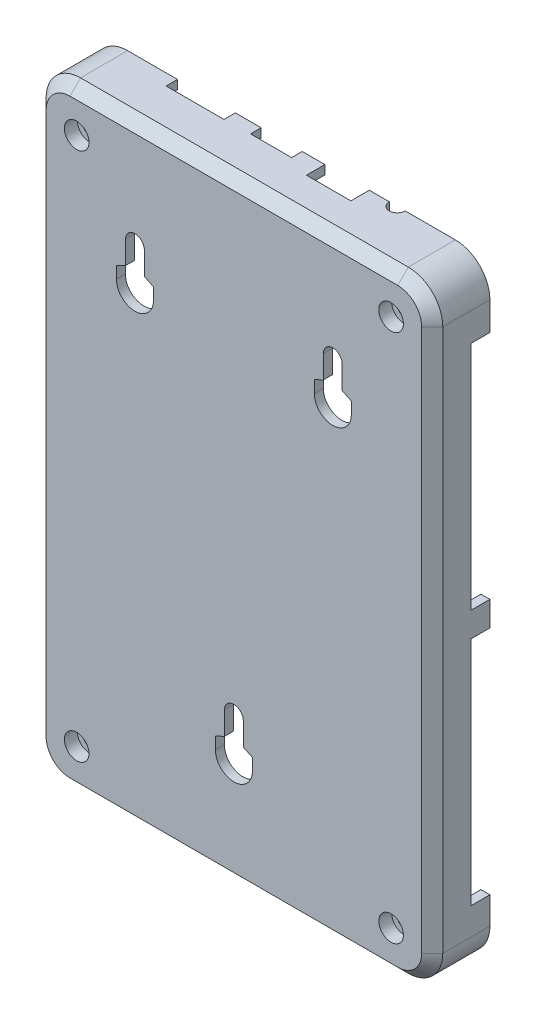
SolidWorks part; units mm, degrees
ref_plane "前基準面" through (0, 0, 0) normal (0, 0, 1) x (1, 0, 0)
ref_plane "上基準面" through (0, 0, 0) normal (0, 1, 0) x (1, 0, 0)
ref_plane "右基準面" through (0, 0, 0) normal (1, 0, 0) x (0, 0, -1)
sketch "草圖1" plane through (0, 0, 0) normal (0, 0, 1) x (1, 0, 0)
  line L0 (-44.3, 60.6) -> (-44.3, -60.6)
  line L1 (-36.6, 60.6) -> (36.6, 60.6) construction
  line L2 (-36.6, 60.6) -> (-36.6, -60.6) construction
  line L3 (-36.6, -60.6) -> (36.6, -60.6) construction
  line L4 (36.6, 60.6) -> (36.6, -60.6) construction
  line L5 (-36.6, 60.6) -> (36.6, -60.6) construction
  line L6 (-36.6, -60.6) -> (36.6, 60.6) construction
  line L7 (-36.6, -68.3) -> (36.6, -68.3)
  line L8 (44.3, -60.6) -> (44.3, 60.6)
  line L9 (36.6, 68.3) -> (-36.6, 68.3)
  arc A0 (-44.3, 60.6) -> (-36.6, 68.3) centre (-36.6, 60.6) cw
  arc A1 (36.6, 68.3) -> (44.3, 60.6) centre (36.6, 60.6) cw
  arc A2 (44.3, -60.6) -> (36.6, -68.3) centre (36.6, -60.6) cw
  arc A3 (-36.6, -68.3) -> (-44.3, -60.6) centre (-36.6, -60.6) cw
  point P0 (0, 0)
  dimension "D3" = 7.7
  dimension "D1" = 121.2
  dimension "D2" = 73.2
  dimension "D4" = 7.7
  dimension "D5" = 7.7
  dimension "D6" = 7.7
  dimension "D7" = 7.7
extrude "填料-伸長1" add sketch "草圖1" along normal blind 12.88
chamfer "導角1" distance 2.36 angle 45 8 edges at (-44.3, 0, 12.88) (0, 68.3, 12.88) (42.0447, 66.0447, 12.88) (44.3, 0, 12.88) (42.0447, -66.0447, 12.88) (0, -68.3, 12.88) (-42.0447, -66.0447, 12.88) (-42.0447, 66.0447, 12.88)
sketch "草圖7" plane through (0, -68.3, 0) normal (0, -1, 0) x (-1, 0, 0)
  line L0 (24.93, 0) -> (14.87, 0) construction
  line L1 (36.6, 0) -> (-36.6, 0) construction
  line L2 (24.93, -5.15) -> (14.87, -5.15)
  line L3 (24.93, 5.15) -> (14.87, 5.15)
  line L7 (36.6, -10.52) -> (36.6, 0) construction
  arc A0 (24.93, -5.15) -> (24.93, 5.15) centre (24.93, 0) ccw
  arc A1 (14.87, 5.15) -> (14.87, -5.15) centre (14.87, 0) ccw
  point P4 (19.9, 0)
  point P9 (30.08, 0)
  dimension "D2" = 5.15
  dimension "D3" = 6.52
  dimension "D1" = 10.06
extrude "除料-伸長4" cut sketch "草圖7" against normal blind 1.13
shell "薄殼1" thickness 2 removed face at (-6.6333, -22.5783, 0)
sketch "草圖2" plane through (0, 0, 12.88) normal (0, 0, 1) x (1, 0, 0)
  line L0 (-26.23, 35.7246) -> (-26.23, 38.3946)
  line L1 (-26.23, 38.3946) -> (-24.2024, 39.37)
  line L2 (44.3, 60.6) -> (44.3, -60.6) construction
  line L3 (-17.97, 35.7246) -> (-17.97, 38.3946)
  line L4 (-17.97, 38.3946) -> (-19.9976, 39.37)
  line L5 (-24.2024, 39.37) -> (-24.2024, 44.5)
  line L6 (-19.9976, 39.37) -> (-19.9976, 44.5)
  line L7 (-24.2024, 44.5) -> (-19.9976, 44.5) construction
  line L8 (36.6, -68.3) -> (-36.6, -68.3) construction
  line L9 (17.97, 35.7246) -> (17.97, 38.3946)
  line L10 (17.97, 38.3946) -> (19.9976, 39.37)
  line L11 (19.9976, 39.37) -> (19.9976, 44.5)
  line L12 (26.23, 35.7246) -> (26.23, 38.3946)
  line L13 (26.23, 38.3946) -> (24.2024, 39.37)
  line L14 (24.2024, 39.37) -> (24.2024, 44.5)
  line L15 (4.13, -44.2754) -> (4.13, -41.6054)
  line L16 (4.13, -41.6054) -> (2.1024, -40.63)
  line L17 (2.1024, -40.63) -> (2.1024, -35.5)
  line L18 (-4.13, -44.2754) -> (-4.13, -41.6054)
  line L19 (-4.13, -41.6054) -> (-2.1024, -40.63)
  line L20 (-2.1024, -40.63) -> (-2.1024, -35.5)
  line L21 (-2.1024, -35.5) -> (2.1024, -35.5) construction
  line L22 (19.9976, 44.5) -> (24.2024, 44.5) construction
  arc A3 (-26.23, 35.7246) -> (-17.97, 35.7246) centre (-22.1, 35.7246) ccw
  arc A4 (26.23, 35.7246) -> (17.97, 35.7246) centre (22.1, 35.7246) cw
  arc A5 (4.13, -44.2754) -> (-4.13, -44.2754) centre (0, -44.2754) cw
  arc A6 (-24.2024, 44.5) -> (-19.9976, 44.5) centre (-22.1, 44.5) cw
  arc A7 (19.9976, 44.5) -> (24.2024, 44.5) centre (22.1, 44.5) cw
  arc A8 (-2.1024, -35.5) -> (2.1024, -35.5) centre (0, -35.5) cw
  dimension "D1" = 4.13
  dimension "D10" = 80
  dimension "D15" = 32.8
  dimension "D2" = 2.67
  dimension "D3" = 2.25
  dimension "D4" = 22.2
  dimension "D5" = 44.2
  dimension "D6" = 44.3
  dimension "D7" = 115.69
  dimension "D8" = 115.69
  dimension "D9" = 5.13
  dimension "D11" = 115.69
  dimension "D12" = 115.69
  dimension "D13" = 115.69
  dimension "D14" = 115.69
extrude "除料-伸長1" cut sketch "草圖2" against normal blind 4.34 contours A6 L5 L1 L0 A3 L3 L4 L6 | A7 L11 L10 L9 A4 L12 L13 L14 | A8 L20 L19 L18 A5 L15 L16 L17 region at (-22.1, 38.1508, 12.88) region at (22.1, 38.1508, 12.88) region at (0, -41.8492, 12.88)
sketch "草圖8" plane through (0, -67.17, 0) normal (0, -1, 0) x (-1, 0, 0)
  line L0 (9.72, 0) -> (30.08, 0) construction
  circle A0 centre (14.87, 0) radius 1.93
  dimension "D1" = 3.86
extrude "除料-伸長5" cut sketch "草圖8" against normal up to next
pattern_linear "直線複製排列1" count 2 spacing 10.06 along (-1, 0, 0) of "除料-伸長5"
sketch "草圖9" plane through (44.3, 0, 0) normal (1, 0, 0) x (0, 0, -1)
  line L0 (0, -60.6) -> (0, 60.6) construction
  line L1 (0, -54.52) -> (-4.17, -54.52)
  line L2 (0, -54.52) -> (0, -2.91)
  line L3 (0, -2.91) -> (-4.17, -2.91)
  line L4 (-4.17, -54.52) -> (-4.17, -2.91)
  line L5 (-10.52, -68.3) -> (0, -68.3) construction
  dimension "D1" = 4.17
  dimension "D2" = 13.78
  dimension "D3" = 51.61
extrude "除料-伸長6" cut sketch "草圖9" against normal up to next
pattern_linear "直線複製排列2" count 2 spacing 57.15 along (0, 1, 0) of "除料-伸長6"
sketch "草圖11" plane through (0, 68.3, 0) normal (0, 1, 0) x (1, 0, 0)
  line L0 (36.6, 0) -> (-36.6, 0) construction
  line L1 (44.3, -10.52) -> (44.3, 0) construction
  circle A0 centre (23.61, 0) radius 1.78
  dimension "D1" = 3.56
  dimension "D2" = 20.69
extrude "除料-伸長7" cut sketch "草圖11" against normal up to next
sketch "草圖12" plane through (0, 68.3, 0) normal (0, 1, 0) x (1, 0, 0)
  line L0 (21.83, 0) -> (-36.6, 0) construction
  line L1 (17.37, 0) -> (7.45, 0)
  line L2 (17.37, 0) -> (17.37, -4.12)
  line L3 (17.37, -4.12) -> (7.45, -4.12)
  line L4 (7.45, 0) -> (7.45, -4.12)
  arc A0 (21.83, 0) -> (25.39, 0) centre (23.61, 0) ccw construction
  dimension "D3" = 6.24
  dimension "D1" = 4.12
  dimension "D2" = 9.92
extrude "除料-伸長8" cut sketch "草圖12" against normal up to next
sketch "草圖13" plane through (0, 68.3, 0) normal (0, 1, 0) x (1, 0, 0)
  line L0 (7.45, 0) -> (-36.6, 0) construction
  line L1 (2.38, 0) -> (-6.79, 0)
  line L2 (2.38, 0) -> (2.38, -2.37)
  line L3 (2.38, -2.37) -> (-6.79, -2.37)
  line L4 (-6.79, 0) -> (-6.79, -2.37)
  dimension "D1" = 5.07
  dimension "D2" = 9.17
  dimension "D3" = 2.37
extrude "除料-伸長9" cut sketch "草圖13" against normal up to next
sketch "草圖14" plane through (0, 68.3, 0) normal (0, 1, 0) x (1, 0, 0)
  line L0 (-6.79, 0) -> (-36.6, 0) construction
  line L1 (-12.55, 0) -> (-25.48, 0)
  line L2 (-12.55, 0) -> (-12.55, -2.54)
  line L3 (-12.55, -2.54) -> (-25.48, -2.54)
  line L4 (-25.48, 0) -> (-25.48, -2.54)
  line L5 (-6.79, 0) -> (-6.79, -2.37) construction
  dimension "D1" = 12.93
  dimension "D2" = 2.54
  dimension "D3" = 5.76
extrude "除料-伸長10" cut sketch "草圖14" against normal up to next
sketch "草圖15" plane through (0, 0, 0) normal (0, 0, -1) x (-1, 0, 0)
  line L0 (44.3, 60.6) -> (44.3, -60.6) construction
  line L1 (44.3, 53.4) -> (42.3, 53.4)
  line L2 (44.3, 53.4) -> (44.3, -52.98)
  line L3 (44.3, -52.98) -> (42.3, -52.98)
  line L4 (42.3, 53.4) -> (42.3, -52.98)
  line L6 (42.3, 60.6) -> (42.3, -60.6) construction
  arc A0 (36.6, -68.3) -> (44.3, -60.6) centre (36.6, -60.6) ccw construction
  dimension "D1" = 7.62
  dimension "D2" = 14.9
extrude "填料-伸長2" add sketch "草圖15" along normal blind 3.16
sketch "草圖16" plane through (-44.3, 0, 0) normal (-1, 0, 0) x (0, 0, 1)
  line L1 (-3.16, 53.4) -> (4.5, 53.4)
  line L2 (-3.16, 53.4) -> (-3.16, -25.03)
  line L3 (-3.16, -25.03) -> (4.5, -25.03)
  line L4 (4.5, 53.4) -> (4.5, -25.03)
  line L5 (-3.16, -52.98) -> (-3.16, 53.4) construction
  line L6 (10.52, 68.3) -> (0, 68.3) construction
  dimension "D1" = 7.66
  dimension "D2" = 14.9
  dimension "D3" = 78.43
extrude "除料-伸長11" cut sketch "草圖16" against normal up to next
sketch "草圖17" plane through (-44.3, 0, 0) normal (-1, 0, 0) x (0, 0, 1)
  line L0 (-3.16, -52.98) -> (-3.16, -25.03) construction
  line L1 (-3.16, -52.98) -> (0, -52.98) construction
  circle A0 centre (-3.16, -33.05) radius 3.53
  circle A1 centre (-3.16, -44.48) radius 3.53
  dimension "D1" = 7.06
  dimension "D2" = 7.06
  dimension "D3" = 8.5
  dimension "D4" = 11.43
extrude "除料-伸長12" cut sketch "草圖17" against normal up to next
sketch "草圖18" plane through (0, 0, 10.88) normal (0, 0, -1) x (-1, 0, 0)
  line L0 (36.6, -65.1116) -> (-36.6, -65.1116) construction
  line L1 (41.1116, 60.6) -> (41.1116, -60.6) construction
  line L2 (-41.1116, -60.6) -> (-41.1116, 60.6) construction
  line L3 (-36.6, 65.1116) -> (36.6, 65.1116) construction
  circle A0 centre (35.1116, -59.1116) radius 4.5
  circle A1 centre (-35.1116, -59.1116) radius 4.5
  circle A2 centre (-35.1116, 59.1116) radius 4.5
  circle A3 centre (35.1116, 59.1116) radius 4.5
  dimension "D1" = 9
  dimension "D3" = 6
  dimension "D4" = 6
  dimension "D2" = 6
  dimension "D5" = 6
extrude "填料-伸長3" add sketch "草圖18" along normal up to surface (10.88 mm away) up to face at (15.7013, -63.9079, 0)
hole_wizard "M2.5 六角承窩頭蓋螺釘的柱孔2" positions "3D草圖3" profile "草圖22" counterbore size "M2.5" standard "ISO" end condition through all
sketch3d "3D草圖3"
  circle A0 centre (35.1116, -59.1116, 0) radius 4.5 construction
  circle A1 centre (-35.1116, -59.1116, 0) radius 4.5 construction
  circle A2 centre (-35.1116, 59.1116, 0) radius 4.5 construction
  circle A3 centre (35.1116, 59.1116, 0) radius 4.5 construction
  point P0 (35.1116, -59.1116, 12.88)
  point P2 (-35.1116, -59.1116, 12.88)
  point P4 (-35.1116, 59.1116, 12.88)
  point P6 (35.1116, 59.1116, 12.88)
  point P17 (35.1116, -59.1116, -4.5)
  point P21 (-35.1116, -59.1116, -4.5)
  point P25 (-35.1116, 59.1116, -4.5)
  point P29 (35.1116, 59.1116, -4.5)
sketch "草圖22" plane through (35.1116, -59.1116, 12.88) normal (1, 0, 0) x (0, -1, 0)
  line L0 (0, 0) -> (0, 16.04)
  line L1 (0, 16.04) -> (1.45, 16.04)
  line L3 (1.45, 16.04) -> (1.45, 2.9)
  line L4 (1.45, 2.9) -> (2.75, 2.9)
  line L5 (2.75, 2.9) -> (2.75, 0)
  line L7 (2.75, 0) -> (0, 0)
  line L11 (0, -6.35) -> (0, 107.95) construction
  dimension "貫穿孔直徑" = 2.9
  dimension "貫穿孔深度" = 16.04
  dimension "柱孔直徑" = 5.5
  dimension "柱孔深度" = 2.9
